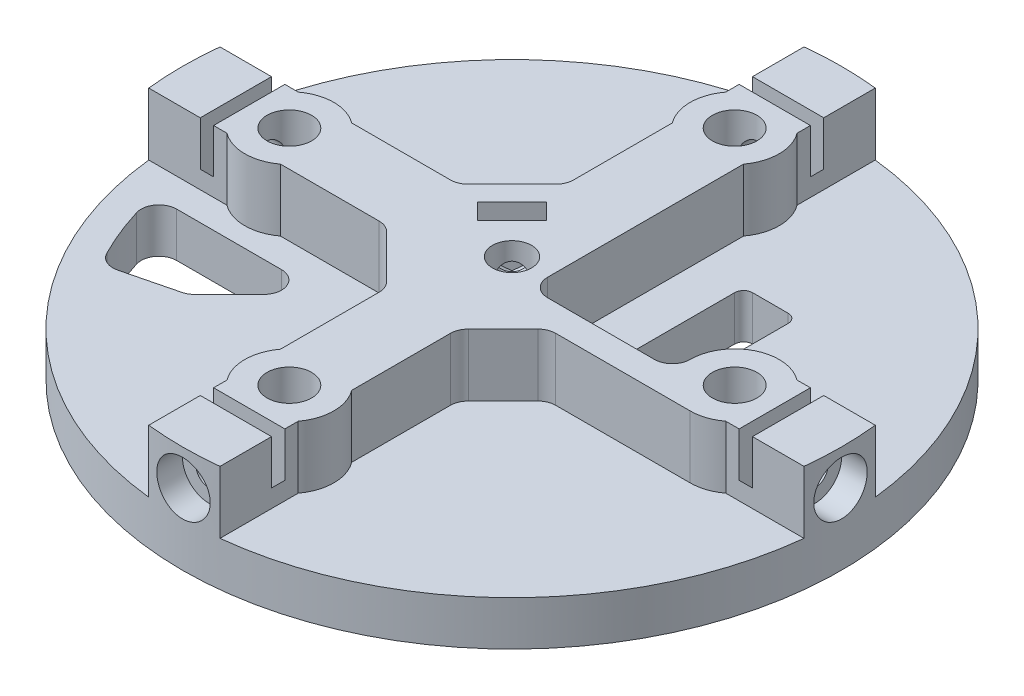
SolidWorks part; units mm, degrees
material "Custom Plastic"
ref_plane "Front Plane" through (0, 0, 0) normal (0, 0, 1) x (1, 0, 0)
ref_plane "Top Plane" through (0, 0, 0) normal (0, 1, 0) x (1, 0, 0)
ref_plane "Right Plane" through (0, 0, 0) normal (1, 0, 0) x (0, 0, -1)
sketch "Sketch1" plane through (0, 0, 0) normal (0, 1, 0) x (1, 0, 0)
  circle A0 centre (0, 0) radius 37
  dimension "D1" = 74
extrude "Boss-Extrude1" add sketch "Sketch1" along normal blind 10
sketch "Sketch5" plane through (0, 10, 0) normal (0, 1, 0) x (1, 0, 0)
  circle A0 centre (0, 0) radius 25 construction
  circle A1 centre (0, 0) radius 37 construction
  point P3 (0, 25)
  point P6 (0, 37)
  point P7 (25, 0)
  point P8 (0, -25)
  point P9 (-25, 0)
  dimension "D1" = 12
  dimension "D2" = 4
hole_wizard "Ø4.0mm Dowel Hole2" positions "Sketch6" profile "Sketch7" hole size "Ø4.0" standard "ANSI Metric"
sketch "Sketch6" plane through (0, 10, 0) normal (0, 1, 0) x (1, 0, 0)
  point P0 (0, 25)
  point P3 (25, 0)
  point P6 (0, -25)
  point P9 (-25, 0)
sketch "Sketch7" plane through (0, 10, -25) normal (1, 0, 0) x (0, 0, 1)
  line L0 (0, 0) -> (0, 9.999)
  line L1 (0, 9.999) -> (2.5, 9.999)
  line L2 (2.5, 9.999) -> (2.5, 0)
  line L5 (2.5, 0) -> (0, 0)
  line L10 (0, 9.999) -> (-2.5, 9.999) construction
  line L11 (0, -6.35) -> (0, 107.95) construction
  dimension "Hole Dia." = 5
  dimension "Hole Depth" = 9.999
  dimension "Drill Angle" = 180
ref_plane "Plane1" through (37, 0, 0) normal (1, 0, 0) x (0, 0, -1)
ref_plane "Plane2" through (26.163, 0, 26.163) normal (0.7071, 0, 0.7071) x (0, -1, 0)
sketch "Sketch19" plane through (0, 10, 0) normal (0, 1, 0) x (1, 0, 0)
  line L0 (-36.7831, -4) -> (-9.6569, -4)
  line L1 (-21.0599, -15.403) -> (-28.838, -23.1812)
  line L2 (-37, 0) -> (0, 0) construction
  line L3 (0, 0) -> (-26.163, -26.163) construction
  line L5 (-4, -36.7831) -> (-4, -9.6569)
  line L7 (-21.0599, -15.403) -> (-15.403, -21.0599)
  line L8 (-15.403, -21.0599) -> (-23.1812, -28.838)
  circle A0 centre (0, 0) radius 37 construction
  arc A1 (-36.7831, -4) -> (-28.838, -23.1812) centre (0, 0) ccw
  arc A2 (-4, -36.7831) -> (-23.1812, -28.838) centre (0, 0) cw
  arc A3 (-9.6569, -4) -> (-4, -9.6569) centre (0, 0) ccw
  point P15 (-18.2314, -18.2314)
  dimension "D1" = 4
  dimension "D2" = 45
  dimension "D3" = 4
  dimension "D4" = 11
extrude "Cut-Extrude3" cut sketch "Sketch19" against normal blind 5
pattern_circular "CirPattern4" count 4 every 90 about axis through (0, 10, 0) along (0, 1, 0) of "Cut-Extrude3"
sketch "Sketch21" plane through (0, 5, 0) normal (0, 1, 0) x (1, 0, 0)
  line L0 (-19.2921, -17.1708) -> (-8.3752, -6.2539)
  line L1 (-21.0599, -15.403) -> (-15.403, -21.0599) construction
  line L2 (-21.0599, -15.403) -> (-15.403, -21.0599) construction
  line L3 (-6.2539, -8.3752) -> (-17.1708, -19.2921)
  line L4 (-26.163, -26.163) -> (0, 0) construction
  line L5 (-19.2921, -17.1708) -> (-17.1708, -19.2921)
  line L6 (0, 0) -> (0, -37) construction
  line L7 (19.2921, -17.1708) -> (8.3752, -6.2539)
  line L8 (19.2921, -17.1708) -> (17.1708, -19.2921)
  line L9 (6.2539, -8.3752) -> (17.1708, -19.2921)
  line L10 (0, 0) -> (37, 0) construction
  line L11 (6.2539, 8.3752) -> (17.1708, 19.2921)
  line L12 (19.2921, 17.1708) -> (17.1708, 19.2921)
  line L13 (19.2921, 17.1708) -> (8.3752, 6.2539)
  line L14 (-19.2921, 17.1708) -> (-8.3752, 6.2539)
  line L15 (-19.2921, 17.1708) -> (-17.1708, 19.2921)
  line L16 (-6.2539, 8.3752) -> (-17.1708, 19.2921)
  arc A0 (-9.6569, -4) -> (-4, -9.6569) centre (0, 0) ccw construction
  arc A1 (-28.838, -23.1812) -> (-23.1812, -28.838) centre (0, 0) ccw construction
  arc A2 (-9.6569, -4) -> (-4, -9.6569) centre (0, 0) ccw construction
  arc A3 (-8.3752, -6.2539) -> (-6.2539, -8.3752) centre (0, 0) ccw
  arc A4 (-4, -36.7831) -> (4, -36.7831) centre (0, 0) ccw construction
  arc A5 (8.3752, -6.2539) -> (6.2539, -8.3752) centre (0, 0) cw
  arc A6 (36.7831, -4) -> (36.7831, 4) centre (0, 0) ccw construction
  arc A7 (8.3752, 6.2539) -> (6.2539, 8.3752) centre (0, 0) ccw
  arc A8 (-8.3752, 6.2539) -> (-6.2539, 8.3752) centre (0, 0) cw
  dimension "D1" = 1.5
  dimension "D2" = 3
extrude "Boss-Extrude5" add sketch "Sketch21" along normal up to surface (5 mm away) up to face at (-22.1589, 10, 22.1589)
chamfer "Chamfer1" distance 3 distance2 5 4 edges at (15.403, 7.5, -21.0599) (21.0599, 7.5, 15.403) (-15.403, 7.5, 21.0599) (-21.0599, 7.5, -15.403) first distance on face at (16.2869, 7.5, -20.176) first distance on face at (20.176, 7.5, 16.2869) first distance on face at (-16.2869, 7.5, 20.176) first distance on face at (-20.176, 7.5, -16.2869)
chamfer "Chamfer2" distance 5 distance2 3 4 edges at (21.0599, 7.5, -15.403) (15.403, 7.5, 21.0599) (-21.0599, 7.5, 15.403) (-15.403, 7.5, -21.0599) first distance on face at (24.949, 7.5, -19.2921) first distance on face at (19.2921, 7.5, 24.949) first distance on face at (-24.949, 7.5, 19.2921) first distance on face at (-19.2921, 7.5, -24.949)
ref_plane "Plane3" through (0, 0, 28.7) normal (0, 0, 1) x (1, 0, 0)
fillet "Fillet15" radius 2 16 edges at (6.2539, 7.5, -8.3752) (8.3752, 7.5, -6.2539) (9.6569, 7.5, -4) (9.6569, 7.5, 4) (8.3752, 7.5, 6.2539) (6.2539, 7.5, 8.3752) (4, 7.5, 9.6569) (-8.3752, 7.5, 6.2539) (-9.6569, 7.5, 4) (-4, 7.5, 9.6569) (-6.2539, 7.5, 8.3752) (4, 7.5, -9.6569) (-4, 7.5, -9.6569) (-6.2539, 7.5, -8.3752) (-8.3752, 7.5, -6.2539) (-9.6569, 7.5, -4)
sketch "Sketch44" plane through (0, 5, 0) normal (0, 1, 0) x (1, 0, 0)
  line L5 (-21.5174, -14.8705) -> (-29.3174, -16.8206)
  line L6 (-24.5954, -18.9385) -> (-19.8814, -17.76) construction
  line L8 (-21.5174, -14.8705) -> (-13.8468, -7.2)
  line L9 (-13.8468, -7.2) -> (-33.0242, -7.2)
  line L10 (-28.4428, -18.2605) -> (-26.2314, -16.0491)
  line L11 (-26.2314, -16.0491) -> (-21.5174, -14.8705)
  line L12 (-21.5174, -14.8705) -> (-13.8468, -7.2)
  line L13 (-13.8468, -7.2) -> (-33.0242, -7.2)
  arc A6 (-33.0242, -7.2) -> (-28.4428, -18.2605) centre (0, 0) ccw
  arc A7 (-33.0242, -7.2) -> (-29.3174, -16.8206) centre (0, 0) ccw
  dimension "D1" = 3.2
extrude "Cut-Extrude12" cut sketch "Sketch44" against normal up to surface (5 mm away) up to face at (0, 0, -22.5)
fillet "Fillet16" radius 2 4 edges at (-33.0242, 2.5, 7.2) (-13.8468, 2.5, 7.2) (-29.3174, 2.5, 16.8206) (-21.5174, 2.5, 14.8705)
sketch "Sketch45" plane through (0, 0, 0) normal (0, -1, 0) x (1, 0, 0)
  circle A0 centre (0, 25) radius 4.2
  circle A1 centre (25, 0) radius 4.2
  circle A2 centre (0, -25) radius 4.2
  circle A3 centre (-25, 0) radius 4.2
  dimension "D1" = 8.4
extrude "Cut-Extrude13" cut sketch "Sketch45" against normal blind 2
sketch "Sketch46" plane through (0, 10, 0) normal (0, 1, 0) x (1, 0, 0)
  circle A0 centre (0, -25) radius 5
  circle A1 centre (0, -25) radius 2.5
  circle A2 centre (0, -25) radius 2.5 construction
  dimension "D1" = 10
extrude "Boss-Extrude6" add sketch "Sketch46" against normal up to surface (5 mm away)
pattern_circular "CirPattern5" count 4 over 270 about axis through (0, 10, 0) along (0, -1, 0) of "Boss-Extrude6" reverse direction yes
ref_plane "Plane4" through (0, 0, 29.5) normal (0, 0, 1) x (1, 0, 0)
sketch "Sketch47" plane through (0, 0, 29.5) normal (0, 0, 1) x (1, 0, 0)
  line L0 (-4, 5) -> (-4, 10)
  line L1 (-4, 10) -> (4, 10)
  line L2 (4, 10) -> (4, 5)
  arc A1 (-4, 5) -> (4, 5) centre (0, 6) ccw
  dimension "D1" = 6
extrude "Cut-Extrude14" cut sketch "Sketch47" along normal blind 1.5
pattern_circular "CirPattern6" count 4 every 90 about axis through (0, 10, 0) along (0, -1, 0) of "Cut-Extrude14" reverse direction yes
hole_wizard "CBORE for M6 Hex Head Bolt1" positions "Sketch48" profile "Sketch49" counterbore size "M6" standard "ANSI Metric"
sketch "Sketch48" plane through (37, 0, 0) normal (1, 0, 0) x (0, 0, -1)
  point P0 (0, 6)
  dimension "D1" = 6
sketch "Sketch49" plane through (37, 6, 0) normal (0, 1, 0) x (0, 0, -1)
  line L0 (0, 0) -> (0, 11)
  line L1 (0, 11) -> (1.5, 11)
  line L2 (1.5, 11) -> (1.5, 3)
  line L3 (1.5, 3) -> (3, 3)
  line L4 (3, 3) -> (3, 0)
  line L5 (3, 0) -> (0, 0)
  line L10 (0, 11) -> (-1.5, 11) construction
  line L11 (0, -6.35) -> (0, 107.95) construction
  dimension "Hole Dia." = 3
  dimension "Hole Depth" = 11
  dimension "C'Bore Dia." = 6
  dimension "C'Bore Depth" = 3
  dimension "Drill Angle" = 180
pattern_circular "CirPattern7" count 4 over 270 about axis through (0, 10, 0) along (0, -1, 0) of "CBORE for M6 Hex Head Bolt1" reverse direction yes
sketch "Sketch50" plane through (0, 10, 0) normal (0, 1, 0) x (1, 0, 0)
  circle A0 centre (0, 0) radius 2.2
  dimension "D1" = 4.4
extrude "Cut-Extrude15" cut sketch "Sketch50" against normal offset from surface (8 mm away) 2 up to face at (0, 0, 20.8)
sketch "Sketch54" plane through (0, 10, 0) normal (0, 1, 0) x (1, 0, 0)
  line L0 (19.8814, 17.76) -> (22, 4)
  line L1 (19.8814, 17.76) -> (17.76, 19.8814)
  line L2 (9.0052, -6.5354) -> (4.08, 10.3517)
  line L44 (28, -4) -> (29.5, -4)
  line L45 (29.5, -4) -> (29.5, 4)
  line L46 (29.5, 4) -> (28, 4)
  line L47 (22, 4) -> (10.9117, 4)
  line L48 (9.511, 7.3896) -> (19.8814, 17.76)
  line L49 (19.8814, 17.76) -> (24.5954, 18.9385)
  line L50 (24.5954, 18.9385) -> (28.838, 23.1812)
  line L51 (23.1812, 28.838) -> (18.9385, 24.5954)
  line L52 (18.9385, 24.5954) -> (17.76, 19.8814)
  line L53 (17.76, 19.8814) -> (7.3896, 9.511)
  line L54 (4, 10.9117) -> (4, 22)
  line L55 (4, 28) -> (4, 29.5)
  line L56 (4, 29.5) -> (-4, 29.5)
  line L57 (-4, 29.5) -> (-4, 28)
  line L58 (-4, 22) -> (-4, 10.9117)
  line L59 (-7.3896, 9.511) -> (-17.76, 19.8814)
  line L60 (-17.76, 19.8814) -> (-18.9385, 24.5954)
  line L61 (-18.9385, 24.5954) -> (-23.1812, 28.838)
  line L62 (-28.838, 23.1812) -> (-24.5954, 18.9385)
  line L63 (-24.5954, 18.9385) -> (-19.8814, 17.76)
  line L64 (-19.8814, 17.76) -> (-9.511, 7.3896)
  line L65 (-10.9117, 4) -> (-22, 4)
  line L66 (-28, 4) -> (-29.5, 4)
  line L67 (-29.5, 4) -> (-29.5, -4)
  line L68 (-29.5, -4) -> (-28, -4)
  line L69 (-22, -4) -> (-10.9117, -4)
  line L70 (-9.511, -7.3896) -> (-19.8814, -17.76)
  line L71 (-19.8814, -17.76) -> (-24.5954, -18.9385)
  line L72 (-24.5954, -18.9385) -> (-28.838, -23.1812)
  line L73 (-23.1812, -28.838) -> (-18.9385, -24.5954)
  line L74 (-18.9385, -24.5954) -> (-17.76, -19.8814)
  line L75 (-17.76, -19.8814) -> (-7.3896, -9.511)
  line L76 (-4, -10.9117) -> (-4, -22)
  line L77 (-4, -28) -> (-4, -29.5)
  line L78 (-4, -29.5) -> (4, -29.5)
  line L79 (4, -29.5) -> (4, -28)
  line L80 (4, -22) -> (4, -10.9117)
  line L81 (7.3896, -9.511) -> (17.76, -19.8814)
  line L82 (17.76, -19.8814) -> (18.9385, -24.5954)
  line L83 (18.9385, -24.5954) -> (23.1812, -28.838)
  line L84 (28.838, -23.1812) -> (24.5954, -18.9385)
  line L85 (24.5954, -18.9385) -> (19.8814, -17.76)
  line L86 (19.8814, -17.76) -> (9.511, -7.3896)
  line L87 (10.9117, -4) -> (22, -4)
  line L97 (17.76, 19.8814) -> (7.3896, 9.511)
  line L131 (10.9117, -4) -> (22, -4)
  arc A1 (22, 4) -> (22, -4) centre (25, 0) ccw
  arc A2 (4, 10.9117) -> (5.026, 9.1649) centre (6, 10.9117) ccw construction
  arc A3 (4.08, 10.3517) -> (5.026, 9.1649) centre (6, 10.9117) ccw
  arc A4 (9.1649, -5.026) -> (9.511, -7.3896) centre (10.9252, -5.9754) ccw construction
  arc A5 (9.1649, -5.026) -> (9.0052, -6.5354) centre (10.9252, -5.9754) ccw
  arc A26 (9.1649, 5.026) -> (10.9117, 4) centre (10.9117, 6) ccw
  arc A27 (9.511, 7.3896) -> (9.1649, 5.026) centre (10.9252, 5.9754) ccw
  arc A28 (5.026, 9.1649) -> (7.3896, 9.511) centre (5.9754, 10.9252) ccw
  arc A29 (5.026, 9.1649) -> (7.3896, 9.511) centre (5.9754, 10.9252) ccw
  arc A30 (28, 4) -> (22, 4) centre (25, 0) ccw
  arc A31 (4, 10.9117) -> (5.026, 9.1649) centre (6, 10.9117) ccw
  arc A32 (-5.026, 9.1649) -> (-4, 10.9117) centre (-6, 10.9117) ccw
  arc A33 (28.838, 23.1812) -> (23.1812, 28.838) centre (0, 0) ccw
  arc A34 (-7.3896, 9.511) -> (-5.026, 9.1649) centre (-5.9754, 10.9252) ccw
  arc A35 (-9.1649, 5.026) -> (-9.511, 7.3896) centre (-10.9252, 5.9754) ccw
  arc A36 (4, 22) -> (4, 28) centre (0, 25) ccw
  arc A37 (-4, 28) -> (-4, 22) centre (0, 25) ccw
  arc A38 (-10.9117, 4) -> (-9.1649, 5.026) centre (-10.9117, 6) ccw
  arc A39 (-9.1649, -5.026) -> (-10.9117, -4) centre (-10.9117, -6) ccw
  arc A40 (-23.1812, 28.838) -> (-28.838, 23.1812) centre (0, 0) ccw
  arc A41 (-9.511, -7.3896) -> (-9.1649, -5.026) centre (-10.9252, -5.9754) ccw
  arc A42 (-5.026, -9.1649) -> (-7.3896, -9.511) centre (-5.9754, -10.9252) ccw
  arc A43 (-22, 4) -> (-28, 4) centre (-25, 0) ccw
  arc A44 (-28, -4) -> (-22, -4) centre (-25, 0) ccw
  arc A45 (-4, -10.9117) -> (-5.026, -9.1649) centre (-6, -10.9117) ccw
  arc A46 (5.026, -9.1649) -> (4, -10.9117) centre (6, -10.9117) ccw
  arc A47 (-28.838, -23.1812) -> (-23.1812, -28.838) centre (0, 0) ccw
  arc A48 (7.3896, -9.511) -> (5.026, -9.1649) centre (5.9754, -10.9252) ccw
  arc A49 (9.1649, -5.026) -> (9.511, -7.3896) centre (10.9252, -5.9754) ccw
  arc A50 (-4, -22) -> (-4, -28) centre (0, -25) ccw
  arc A51 (4, -28) -> (4, -22) centre (0, -25) ccw
  arc A54 (23.1812, -28.838) -> (28.838, -23.1812) centre (0, 0) ccw
  arc A57 (22, -4) -> (28, -4) centre (25, 0) ccw
  arc A90 (10.9117, -4) -> (9.1649, -5.026) centre (10.9117, -6) ccw
  arc A91 (10.9117, -4) -> (9.1649, -5.026) centre (10.9117, -6) ccw
  dimension "D1" = 0
extrude "Cut-Extrude18" cut sketch "Sketch54" against normal up to surface (5 mm away) contours L0 A1 L131 A91 A5 L2 A3 A29 L97 L1
sketch "Sketch55" plane through (0, 5, 0) normal (0, 1, 0) x (1, 0, 0)
  line L0 (7.6824, -2) -> (20.4174, -2)
  line L5 (4.08, 10.3517) -> (9.0052, -6.5354) construction
  line L6 (25, -5) -> (11.9497, -5)
  line L9 (19.8814, -17.76) -> (9.511, -7.3896) construction
  line L10 (19.8814, -17.76) -> (9.511, -7.3896) construction
  line L11 (10.5355, -8.4142) -> (9.511, -7.3896)
  line L12 (7.6824, -2) -> (9.0052, -6.5354)
  arc A0 (28, 4) -> (28, -4) centre (25, 0) ccw construction
  arc A1 (28, 4) -> (28, -4) centre (25, 0) ccw construction
  arc A2 (20.4174, -2) -> (25, -5) centre (25, 0) ccw
  arc A3 (11.9497, -5) -> (10.5355, -8.4142) centre (11.9497, -7) ccw
  arc A4 (9.0052, -6.5354) -> (9.511, -7.3896) centre (10.9252, -5.9754) ccw construction
  arc A5 (9.0052, -6.5354) -> (9.511, -7.3896) centre (10.9252, -5.9754) ccw
  dimension "D2" = 4
  dimension "D1" = 2
extrude "Boss-Extrude7" add sketch "Sketch55" along normal up to surface (5 mm away) contours L6 A3 L11 A5 L12 L0 A2 up to face at (0, 10, -33.9458)
sketch "Sketch56" plane through (0, 5, 0) normal (0, 1, 0) x (1, 0, 0)
  line L0 (9, 2) -> (15, 2)
  line L1 (15, 2) -> (15, 17)
  line L2 (15, 17) -> (9, 17)
  line L3 (9, 17) -> (9, 2)
  line L4 (7.6824, -2) -> (20.4174, -2) construction
  dimension "D1" = 9
  dimension "D2" = 6
  dimension "D3" = 4
  dimension "D4" = 15
extrude "Cut-Extrude19" cut sketch "Sketch56" against normal blind 5
fillet "Fillet19" radius 2 4 edges at (20.4174, 7.5, 2) (7.6824, 7.5, 2) (19.8814, 7.5, -17.76) (17.76, 7.5, -19.8814)
fillet "Fillet20" radius 1 4 edges at (15, 2.5, -17) (9, 2.5, -17) (15, 2.5, -2) (9, 2.5, -2)
sketch "Sketch58" plane through (0, 10, 0) normal (0, 1, 0) x (1, 0, 0)
  line L0 (9.1824, -2) -> (18, -2) construction
  line L1 (28, 4) -> (29.5, 4) construction
  line L2 (29.5, 4) -> (31, 4) construction
  line L3 (31, 4) -> (36.7831, 4) construction
  line L6 (11.9497, -5) -> (9.9117, -5)
  line L8 (0, -1000) -> (0, 49000) construction
  line L9 (4, 36.7831) -> (4, 31) construction
  line L10 (4, 31) -> (4, 29.5) construction
  line L11 (4, 29.5) -> (4, 28) construction
  line L12 (4, 22) -> (4, 10.9117) construction
  line L14 (25, -5) -> (11.9497, -5) construction
  line L15 (8.4975, -5.5858) -> (4.5858, -9.4975)
  line L18 (36.7831, -4) -> (31, -4) construction
  line L19 (31, -4) -> (29.5, -4) construction
  line L20 (29.5, -4) -> (28, -4) construction
  line L21 (4, -28) -> (4, -29.5) construction
  line L22 (4, -29.5) -> (4, -31) construction
  line L23 (4, -31) -> (4, -36.7831) construction
  line L27 (4, -10.9117) -> (4, -22) construction
  line L28 (-28, -4) -> (-29.5, -4) construction
  line L29 (-29.5, -4) -> (-31, -4) construction
  line L30 (-31, -4) -> (-36.7831, -4) construction
  line L34 (-10.9117, -4) -> (-22, -4) construction
  line L35 (-4, -22) -> (-4, -10.9117) construction
  line L39 (-4, -36.7831) -> (-4, -31) construction
  line L40 (-4, -31) -> (-4, -29.5) construction
  line L41 (-4, -29.5) -> (-4, -28) construction
  line L42 (-4, 28) -> (-4, 29.5) construction
  line L43 (-4, 29.5) -> (-4, 31) construction
  line L44 (-4, 31) -> (-4, 36.7831) construction
  line L48 (-4, 10.9117) -> (-4, 22) construction
  line L49 (-22, 4) -> (-10.9117, 4) construction
  line L53 (-36.7831, 4) -> (-31, 4) construction
  line L54 (-31, 4) -> (-29.5, 4) construction
  line L55 (-29.5, 4) -> (-28, 4) construction
  line L56 (6, -2) -> (18, -2)
  line L57 (28, 4) -> (29.5, 4)
  line L58 (29.5, 4) -> (31, 4)
  line L59 (31, 4) -> (36.7831, 4)
  line L65 (4, 36.7831) -> (4, 31)
  line L66 (4, 31) -> (4, 29.5)
  line L67 (4, 29.5) -> (4, 28)
  line L68 (4, 22) -> (4, 0)
  line L70 (25, -5) -> (11.9497, -5)
  line L74 (36.7831, -4) -> (31, -4)
  line L75 (31, -4) -> (29.5, -4)
  line L76 (29.5, -4) -> (28, -4)
  line L77 (4, -28) -> (4, -29.5)
  line L78 (4, -29.5) -> (4, -31)
  line L79 (4, -31) -> (4, -36.7831)
  line L83 (4, -10.9117) -> (4, -22)
  line L84 (-28, -4) -> (-29.5, -4)
  line L85 (-29.5, -4) -> (-31, -4)
  line L86 (-31, -4) -> (-36.7831, -4)
  line L90 (-10.9117, -4) -> (-22, -4)
  line L91 (-4, -22) -> (-4, -10.9117)
  line L95 (-4, -36.7831) -> (-4, -31)
  line L96 (-4, -31) -> (-4, -29.5)
  line L97 (-4, -29.5) -> (-4, -28)
  line L98 (-4, 28) -> (-4, 29.5)
  line L99 (-4, 29.5) -> (-4, 31)
  line L100 (-4, 31) -> (-4, 36.7831)
  line L104 (-4, 10.9117) -> (-4, 22)
  line L105 (-22, 4) -> (-10.9117, 4)
  line L109 (-36.7831, 4) -> (-31, 4)
  line L110 (-31, 4) -> (-29.5, 4)
  line L111 (-29.5, 4) -> (-28, 4)
  line L112 (-9.4975, 4.5858) -> (-4.5858, 9.4975)
  line L113 (-9.4975, -4.5858) -> (-4.5858, -9.4975)
  arc A0 (18, -2) -> (20, 0) centre (18, 0) ccw construction
  arc A1 (28, 4) -> (20, 0) centre (25, 0) ccw construction
  arc A2 (36.7831, 4) -> (28.838, 23.1812) centre (0, 0) ccw construction
  arc A5 (23.1812, 28.838) -> (4, 36.7831) centre (0, 0) ccw construction
  arc A6 (4, 22) -> (4, 28) centre (0, 25) ccw construction
  arc A10 (28.838, -23.1812) -> (36.7831, -4) centre (0, 0) ccw construction
  arc A11 (25, -5) -> (28, -4) centre (25, 0) ccw construction
  arc A12 (4, -28) -> (4, -22) centre (0, -25) ccw construction
  arc A13 (4, -36.7831) -> (23.1812, -28.838) centre (0, 0) ccw construction
  arc A14 (4, -10.9117) -> (4.5858, -9.4975) centre (6, -10.9117) cw
  arc A15 (8.4975, -5.5858) -> (9.9117, -5) centre (9.9117, -7) cw
  arc A16 (-28, -4) -> (-22, -4) centre (-25, 0) ccw construction
  arc A17 (-36.7831, -4) -> (-28.838, -23.1812) centre (0, 0) ccw construction
  arc A19 (-9.1649, -5.026) -> (-10.9117, -4) centre (-10.9117, -6) ccw construction
  arc A20 (-4, -22) -> (-4, -28) centre (0, -25) ccw construction
  arc A21 (-4, -10.9117) -> (-5.026, -9.1649) centre (-6, -10.9117) ccw construction
  arc A22 (6, -2) -> (4, 0) centre (6, 0) cw
  arc A23 (-23.1812, -28.838) -> (-4, -36.7831) centre (0, 0) ccw construction
  arc A24 (-4, 28) -> (-4, 22) centre (0, 25) ccw construction
  arc A25 (-4, 36.7831) -> (-23.1812, 28.838) centre (0, 0) ccw construction
  arc A27 (-5.026, 9.1649) -> (-4, 10.9117) centre (-6, 10.9117) ccw construction
  arc A28 (-22, 4) -> (-28, 4) centre (-25, 0) ccw construction
  arc A29 (-10.9117, 4) -> (-9.1649, 5.026) centre (-10.9117, 6) ccw construction
  arc A31 (-28.838, 23.1812) -> (-36.7831, 4) centre (0, 0) ccw construction
  arc A32 (18, -2) -> (20, 0) centre (18, 0) ccw
  arc A33 (28, 4) -> (20, 0) centre (25, 0) ccw
  arc A34 (36.7831, 4) -> (23.1812, 28.838) centre (0, 0) ccw
  arc A37 (23.1812, 28.838) -> (4, 36.7831) centre (0, 0) ccw
  arc A38 (4, 22) -> (4, 28) centre (0, 25) ccw
  arc A42 (28.838, -23.1812) -> (36.7831, -4) centre (0, 0) ccw
  arc A43 (25, -5) -> (28, -4) centre (25, 0) ccw
  arc A44 (4, -28) -> (4, -22) centre (0, -25) ccw
  arc A45 (4, -36.7831) -> (28.838, -23.1812) centre (0, 0) ccw
  arc A48 (-28, -4) -> (-22, -4) centre (-25, 0) ccw
  arc A49 (-36.7831, -4) -> (-23.1812, -28.838) centre (0, 0) ccw
  arc A51 (-9.4975, -4.5858) -> (-10.9117, -4) centre (-10.9117, -6) ccw
  arc A52 (-4, -22) -> (-4, -28) centre (0, -25) ccw
  arc A53 (-4, -10.9117) -> (-4.5858, -9.4975) centre (-6, -10.9117) ccw
  arc A55 (-23.1812, -28.838) -> (-4, -36.7831) centre (0, 0) ccw
  arc A56 (-4, 28) -> (-4, 22) centre (0, 25) ccw
  arc A57 (-4, 36.7831) -> (-28.838, 23.1812) centre (0, 0) ccw
  arc A59 (-4.5858, 9.4975) -> (-4, 10.9117) centre (-6, 10.9117) ccw
  arc A60 (-22, 4) -> (-28, 4) centre (-25, 0) ccw
  arc A61 (-10.9117, 4) -> (-9.4975, 4.5858) centre (-10.9117, 6) ccw
  arc A63 (-28.838, 23.1812) -> (-36.7831, 4) centre (0, 0) ccw
  dimension "D2" = 2
  dimension "D1" = 2
extrude "Cut-Extrude20" cut sketch "Sketch58" against normal up to surface (5 mm away)
hole_wizard "Ø1.0mm Dowel Hole2" positions "Sketch59" profile "Sketch60" hole size "Ø1.0" standard "ANSI Metric"
sketch "Sketch59" plane through (-7.0416, 0, -7.0416) normal (-0.7071, 0, -0.7071) x (-0.7071, 0, 0.7071)
  line L0 (0, 10) -> (0, 5) construction
  line L1 (3.4731, 10) -> (-3.4731, 10) construction
  line L2 (23.1812, 5) -> (-23.1812, 5) construction
  point P0 (0, 6.5)
  point P9 (0, 6.584)
  dimension "D1" = 1.5
sketch "Sketch60" plane through (-7.0416, 6.5, -7.0416) normal (0, 1, 0) x (-0.7071, 0, 0.7071)
  line L0 (0, 0) -> (0, 10)
  line L1 (0, 10) -> (1.5, 10)
  line L2 (1.5, 10) -> (1.5, 0)
  line L5 (1.5, 0) -> (0, 0)
  line L10 (0, 10) -> (-1.5, 10) construction
  line L11 (0, -6.35) -> (0, 107.95) construction
  dimension "Hole Dia." = 3
  dimension "Hole Depth" = 10
  dimension "Drill Angle" = 180
sketch "Sketch61" plane through (0, 5, 0) normal (0, 1, 0) x (1, 0, 0)
  line L0 (6, -2) -> (18, -2) construction
  line L1 (10, 2) -> (14, 2) construction
  line L2 (9, -2) -> (15, -2)
  line L3 (10, 2) -> (14, 2)
  line L4 (9, 3) -> (9, -2)
  line L5 (15, 3) -> (15, -2)
  arc A0 (14, 2) -> (15, 3) centre (14, 3) ccw construction
  arc A1 (9, 3) -> (10, 2) centre (10, 3) ccw construction
  arc A2 (14, 2) -> (15, 3) centre (14, 3) ccw
  arc A3 (9, 3) -> (10, 2) centre (10, 3) ccw
extrude "Cut-Extrude21" cut sketch "Sketch61" against normal blind 4
ref_plane "Plane5" through (0, 0, 0) normal (0.7071, 0, 0.7071) x (0.7071, 0, -0.7071)
ref_plane "Plane6" through (-3.5355, 0, -3.5355) normal (0.7071, 0, 0.7071) x (0.7071, 0, -0.7071)
sketch "Sketch63" plane through (-3.5355, 0, -3.5355) normal (0.7071, 0, 0.7071) x (0.7071, 0, -0.7071)
  line L0 (0, 5) -> (0, 10) construction
  line L2 (-2.75, 10) -> (-2.75, 4.9123)
  line L3 (-2.75, 4.9123) -> (0, 3.3246)
  line L4 (0, 3.3246) -> (2.75, 4.9123)
  line L5 (2.75, 4.9123) -> (2.75, 10)
  line L7 (23.1812, 5) -> (-23.1812, 5) construction
  line L8 (2.0589, 10) -> (-3.4731, 10) construction
  line L9 (-9.9584, 10) -> (-10.5442, 10) construction
  line L10 (-1.0861, 9.0484) -> (-2.4611, 8.2545) [skipped]
  line L11 (1.0861, 9.0484) -> (-0.2889, 9.8422) [skipped]
  line L12 (-2.75, 10) -> (2.75, 10)
  line L13 (-3.4731, 5) -> (2.0589, 5) construction
  circle A0 centre (0, 6.5) radius 2.75 construction
  point P1 (0, 6.8328)
  dimension "D1" = 5.5
  dimension "D2" = 1.5
extrude "Cut-Extrude22" cut sketch "Sketch63" against normal blind 2.5
chamfer "Chamfer3" distance 1.7 angle 45 4 edges at (25, 2, -2.5) (0, 2, 22.5) (-25, 2, -2.5) (0, 2, -27.5)
sketch "Sketch64" plane through (0, 0, 0) normal (0, -1, 0) x (1, 0, 0)
  line L3 (-30.4401, 7.2) -> (-18.6752, 7.2)
  line L4 (-22.0548, 15.0049) -> (-27.8144, 16.4448)
  line L5 (-17.261, 10.6142) -> (-21.1256, 14.4788)
  line L6 (-30.4401, 7.2) -> (-18.6752, 7.2)
  line L7 (-22.0548, 15.0049) -> (-27.8144, 16.4448)
  line L8 (-17.261, 10.6142) -> (-21.1256, 14.4788)
  line L10 (15, -16) -> (15, -3)
  line L11 (10, -17) -> (14, -17)
  line L12 (9, -3) -> (9, -16)
  line L13 (14, -2) -> (10, -2)
  line L14 (15, -16) -> (15, -3)
  line L15 (10, -17) -> (14, -17)
  line L16 (9, -3) -> (9, -16)
  line L17 (14, -2) -> (10, -2)
  circle A0 centre (0, 0) radius 37 construction
  circle A1 centre (-25, 0) radius 4.2
  circle A3 centre (-25, 0) radius 4.2
  circle A4 centre (0, -25) radius 4.2
  circle A5 centre (0, -25) radius 4.2
  arc A6 (-32.3546, 9.7786) -> (-30.4401, 7.2) centre (-30.4401, 9.2) ccw
  arc A7 (-30.0793, 15.4168) -> (-32.3546, 9.7786) centre (0, 0) ccw
  arc A8 (-27.8144, 16.4448) -> (-30.0793, 15.4168) centre (-28.2995, 14.5045) ccw
  arc A9 (-21.1256, 14.4788) -> (-22.0548, 15.0049) centre (-22.5399, 13.0646) ccw
  arc A10 (-18.6752, 7.2) -> (-17.261, 10.6142) centre (-18.6752, 9.2) ccw
  arc A11 (-32.3546, 9.7786) -> (-30.4401, 7.2) centre (-30.4401, 9.2) ccw
  arc A12 (-30.0793, 15.4168) -> (-32.3546, 9.7786) centre (0, 0) ccw
  arc A13 (-27.8144, 16.4448) -> (-30.0793, 15.4168) centre (-28.2995, 14.5045) ccw
  arc A14 (-21.1256, 14.4788) -> (-22.0548, 15.0049) centre (-22.5399, 13.0646) ccw
  arc A15 (-18.6752, 7.2) -> (-17.261, 10.6142) centre (-18.6752, 9.2) ccw
  circle A16 centre (25, 0) radius 4.2
  circle A17 centre (25, 0) radius 4.2
  circle A18 centre (0, 25) radius 4.2
  circle A19 centre (0, 25) radius 4.2
  circle A20 centre (0, 0) radius 37
  arc A23 (14, -17) -> (15, -16) centre (14, -16) ccw
  arc A24 (9, -16) -> (10, -17) centre (10, -16) ccw
  arc A25 (10, -2) -> (9, -3) centre (10, -3) ccw
  arc A26 (15, -3) -> (14, -2) centre (14, -3) ccw
  arc A27 (14, -17) -> (15, -16) centre (14, -16) ccw
  arc A28 (9, -16) -> (10, -17) centre (10, -16) ccw
  arc A29 (10, -2) -> (9, -3) centre (10, -3) ccw
  arc A30 (15, -3) -> (14, -2) centre (14, -3) ccw
  dimension "D1" = 0
  dimension "D2" = 0
  dimension "D3" = 0
  dimension "D4" = 0
  dimension "D5" = 0
  dimension "D6" = 0
extrude "Boss-Extrude8" add sketch "Sketch64" along normal blind 2
sketch "Sketch65" plane through (0, 5, 0) normal (0, 1, 0) x (1, 0, 0)
  line L0 (-4, -36.7831) -> (-4, -31) construction
  line L1 (-4, -31) -> (-4, -29.5) construction
  line L2 (-4, -29.5) -> (-4, -28) construction
  line L3 (-4, -22) -> (-4, -10.9117) construction
  line L4 (-4.5858, -9.4975) -> (-9.4975, -4.5858) construction
  line L5 (-10.9117, -4) -> (-22, -4) construction
  line L6 (-28, -4) -> (-29.5, -4) construction
  line L7 (-29.5, -4) -> (-31, -4) construction
  line L8 (-31, -4) -> (-36.7831, -4) construction
  line L9 (36.7831, -4) -> (31, -4) construction
  line L10 (31, -4) -> (29.5, -4) construction
  line L11 (29.5, -4) -> (28, -4) construction
  line L12 (25, -5) -> (9.9117, -5) construction
  line L13 (8.4975, -5.5858) -> (4.5858, -9.4975) construction
  line L14 (4, -10.9117) -> (4, -22) construction
  line L15 (4, -28) -> (4, -29.5) construction
  line L16 (4, -29.5) -> (4, -31) construction
  line L17 (4, -31) -> (4, -36.7831) construction
  line L18 (15, 16) -> (15, -2) construction
  line L19 (15, -2) -> (18, -2) construction
  line L20 (28, 4) -> (29.5, 4) construction
  line L21 (29.5, 4) -> (31, 4) construction
  line L22 (31, 4) -> (36.7831, 4) construction
  line L23 (4, 36.7831) -> (4, 31) construction
  line L24 (4, 31) -> (4, 29.5) construction
  line L25 (4, 29.5) -> (4, 28) construction
  line L26 (4, 22) -> (4, 0) construction
  line L27 (6, -2) -> (9, -2) construction
  line L28 (9, -2) -> (9, 16) construction
  line L29 (10, 17) -> (14, 17) construction
  line L39 (-4, -36.7831) -> (-4, -31)
  line L40 (-4, -31) -> (-4, -29.5)
  line L41 (-4, -29.5) -> (-4, -28)
  line L42 (-4, -22) -> (-4, -10.9117)
  line L43 (-4.5858, -9.4975) -> (-9.4975, -4.5858)
  line L44 (-10.9117, -4) -> (-22, -4)
  line L45 (-28, -4) -> (-29.5, -4)
  line L46 (-29.5, -4) -> (-31, -4)
  line L47 (-31, -4) -> (-36.7831, -4)
  line L48 (36.7831, -4) -> (31, -4)
  line L49 (31, -4) -> (29.5, -4)
  line L50 (29.5, -4) -> (28, -4)
  line L51 (25, -5) -> (9.9117, -5)
  line L52 (8.4975, -5.5858) -> (4.5858, -9.4975)
  line L53 (4, -10.9117) -> (4, -22)
  line L54 (4, -28) -> (4, -29.5)
  line L55 (4, -29.5) -> (4, -31)
  line L56 (4, -31) -> (4, -36.7831)
  line L57 (15, 16) -> (15, -2)
  line L58 (15, -2) -> (18, -2)
  line L59 (28, 4) -> (29.5, 4)
  line L60 (29.5, 4) -> (31, 4)
  line L61 (31, 4) -> (36.7831, 4)
  line L62 (4, 36.7831) -> (4, 31)
  line L63 (4, 31) -> (4, 29.5)
  line L64 (4, 29.5) -> (4, 28)
  line L65 (4, 22) -> (4, 0)
  line L66 (6, -2) -> (9, -2)
  line L67 (9, -2) -> (9, 16)
  line L68 (10, 17) -> (14, 17)
  line L88 (-36.7831, 4) -> (-31, 4)
  line L89 (-31, 4) -> (-29.5, 4)
  line L90 (-29.5, 4) -> (-28, 4)
  line L91 (-22, 4) -> (-10.9117, 4)
  line L92 (-9.4975, 4.5858) -> (-7.0416, 7.0416)
  line L93 (-7.0416, 7.0416) -> (-4.5858, 9.4975)
  line L94 (-4, 10.9117) -> (-4, 22)
  line L95 (-4, 28) -> (-4, 29.5)
  line L96 (-4, 29.5) -> (-4, 31)
  line L97 (-4, 31) -> (-4, 36.7831)
  line L98 (-36.7831, 4) -> (-31, 4)
  line L99 (-31, 4) -> (-29.5, 4)
  line L100 (-29.5, 4) -> (-28, 4)
  line L101 (-22, 4) -> (-10.9117, 4)
  line L102 (-9.4975, 4.5858) -> (-7.0416, 7.0416)
  line L103 (-7.0416, 7.0416) -> (-4.5858, 9.4975)
  line L104 (-4, 10.9117) -> (-4, 22)
  line L105 (-4, 28) -> (-4, 29.5)
  line L106 (-4, 29.5) -> (-4, 31)
  line L107 (-4, 31) -> (-4, 36.7831)
  arc A0 (-36.7831, -4) -> (-4, -36.7831) centre (0, 0) ccw construction
  arc A1 (-4, -22) -> (-4, -28) centre (0, -25) ccw construction
  arc A2 (-4, -10.9117) -> (-4.5858, -9.4975) centre (-6, -10.9117) ccw construction
  arc A3 (-9.4975, -4.5858) -> (-10.9117, -4) centre (-10.9117, -6) ccw construction
  arc A4 (-28, -4) -> (-22, -4) centre (-25, 0) ccw construction
  arc A5 (4, -36.7831) -> (36.7831, -4) centre (0, 0) ccw construction
  arc A6 (25, -5) -> (28, -4) centre (25, 0) ccw construction
  arc A7 (9.9117, -5) -> (8.4975, -5.5858) centre (9.9117, -7) ccw construction
  arc A8 (4.5858, -9.4975) -> (4, -10.9117) centre (6, -10.9117) ccw construction
  arc A9 (4, -28) -> (4, -22) centre (0, -25) ccw construction
  arc A10 (18, -2) -> (20, 0) centre (18, 0) ccw construction
  arc A11 (28, 4) -> (20, 0) centre (25, 0) ccw construction
  arc A12 (36.7831, 4) -> (4, 36.7831) centre (0, 0) ccw construction
  arc A13 (4, 22) -> (4, 28) centre (0, 25) ccw construction
  arc A14 (4, 0) -> (6, -2) centre (6, 0) ccw construction
  arc A15 (10, 17) -> (9, 16) centre (10, 16) ccw construction
  arc A16 (15, 16) -> (14, 17) centre (14, 16) ccw construction
  arc A22 (-36.7831, -4) -> (-4, -36.7831) centre (0, 0) ccw
  arc A23 (-4, -22) -> (-4, -28) centre (0, -25) ccw
  arc A24 (-4, -10.9117) -> (-4.5858, -9.4975) centre (-6, -10.9117) ccw
  arc A25 (-9.4975, -4.5858) -> (-10.9117, -4) centre (-10.9117, -6) ccw
  arc A26 (-28, -4) -> (-22, -4) centre (-25, 0) ccw
  arc A27 (4, -36.7831) -> (36.7831, -4) centre (0, 0) ccw
  arc A28 (25, -5) -> (28, -4) centre (25, 0) ccw
  arc A29 (9.9117, -5) -> (8.4975, -5.5858) centre (9.9117, -7) ccw
  arc A30 (4.5858, -9.4975) -> (4, -10.9117) centre (6, -10.9117) ccw
  arc A31 (4, -28) -> (4, -22) centre (0, -25) ccw
  arc A32 (18, -2) -> (20, 0) centre (18, 0) ccw
  arc A33 (28, 4) -> (20, 0) centre (25, 0) ccw
  arc A34 (36.7831, 4) -> (4, 36.7831) centre (0, 0) ccw
  arc A35 (4, 22) -> (4, 28) centre (0, 25) ccw
  arc A36 (4, 0) -> (6, -2) centre (6, 0) ccw
  arc A37 (10, 17) -> (9, 16) centre (10, 16) ccw
  arc A38 (15, 16) -> (14, 17) centre (14, 16) ccw
  arc A49 (-4, 36.7831) -> (-36.7831, 4) centre (0, 0) ccw
  arc A50 (-22, 4) -> (-28, 4) centre (-25, 0) ccw
  arc A51 (-10.9117, 4) -> (-9.4975, 4.5858) centre (-10.9117, 6) ccw
  arc A52 (-4.5858, 9.4975) -> (-4, 10.9117) centre (-6, 10.9117) ccw
  arc A53 (-4, 28) -> (-4, 22) centre (0, 25) ccw
  arc A54 (-4, 36.7831) -> (-36.7831, 4) centre (0, 0) ccw
  arc A55 (-22, 4) -> (-28, 4) centre (-25, 0) ccw
  arc A56 (-10.9117, 4) -> (-9.4975, 4.5858) centre (-10.9117, 6) ccw
  arc A57 (-4.5858, 9.4975) -> (-4, 10.9117) centre (-6, 10.9117) ccw
  arc A58 (-4, 28) -> (-4, 22) centre (0, 25) ccw
  dimension "D1" = 0
extrude "Cut-Extrude23" cut sketch "Sketch65" against normal blind 2
